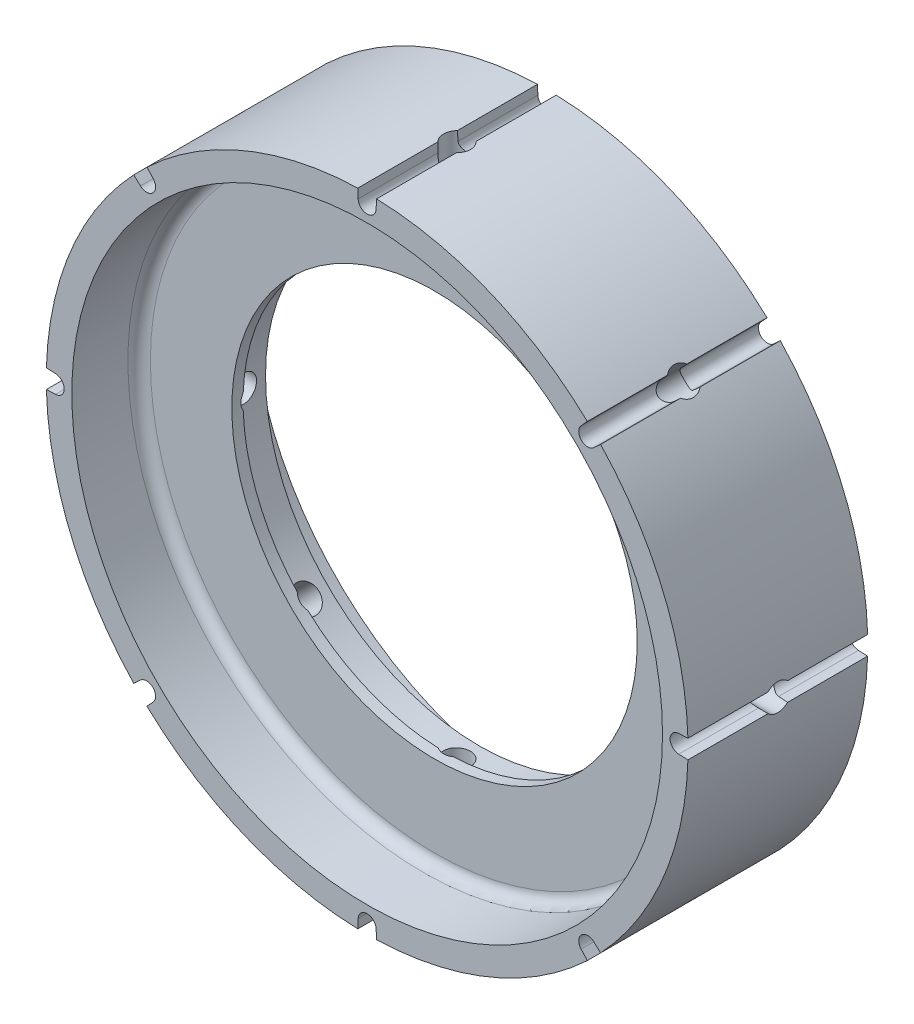
SolidWorks part; units mm, degrees
ref_plane "Front Plane" through (0, 0, 0) normal (0, 0, 1) x (1, 0, 0)
ref_plane "Top Plane" through (0, 0, 0) normal (0, 1, 0) x (1, 0, 0)
ref_plane "Right Plane" through (0, 0, 0) normal (1, 0, 0) x (0, 0, -1)
sketch "Sketch1" plane through (0, 0, 0) normal (0, 0, 1) x (1, 0, 0)
  circle A4 centre (0, 0) radius 14.2875
  circle A5 centre (0, 0) radius 13.15
  circle A6 centre (0, 0) radius 13.15
  dimension "D1" = 0.15
  dimension "D3" = 1.1375
  dimension "D2" = 28.575
extrude "Boss-Extrude1" add sketch "Sketch1" against normal blind 3
sketch "Sketch2" plane through (0, 0, 0) normal (0, 0, 1) x (1, 0, 0)
  circle A0 centre (0, 0) radius 14.2875
  circle A1 centre (0, 0) radius 9.025
  circle A2 centre (0, 0) radius 14.2875 construction
  dimension "D1" = 18.05
extrude "Boss-Extrude2" add sketch "Sketch2" along normal blind 2
sketch "Sketch3" plane through (0, 0, 2) normal (0, 0, 1) x (1, 0, 0)
  circle A0 centre (0, 0) radius 13.15 construction
  circle A1 centre (0, 0) radius 14.2875
  circle A2 centre (0, 0) radius 14.2875
  circle A3 centre (0, 0) radius 13.15
  dimension "D1" = 0
extrude "Boss-Extrude3" add sketch "Sketch3" along normal blind 3
fillet "Fillet1" radius 0.5 2 edges at (13.15, 0, 2) (13.15, 0, 0)
sketch "Sketch4" plane through (0, 0, 0) normal (0, 0, -1) x (-1, 0, 0)
  circle A1 centre (0, 0) radius 9.525
extrude "Cut-Extrude2" cut sketch "Sketch4" against normal blind 1.5
sketch "Sketch5" plane through (0, 0, -3) normal (0, 0, -1) x (-1, 0, 0)
  line L0 (-13.8709, 0.3997) -> (-14.2814, 0.4167)
  line L1 (-13.8709, -0.3997) -> (-14.2814, -0.4167)
  circle A3 centre (0, 0) radius 14.2875 construction
  circle A5 centre (0, 0) radius 14.2875
  circle A6 centre (-13.8875, 0) radius 0.4
  circle M4 centre (0, 0) radius 14.2875
extrude "Cut-Extrude4" cut sketch "Sketch5" against normal through all contours A6 | A6 L0 M4 | A6 A5 L1 region at (14.1918, 0.3195, -3) region at (13.8875, 0, -3) region at (14.1918, -0.3195, -3)
ref_plane "Plane1" through (14.2814, 0, 0) normal (1, 0, 0) x (0, 0, -1)
sketch "Sketch6" plane through (14.2814, 0, 0) normal (1, 0, 0) x (0, 0, -1)
  line L0 (-5, 0.4167) -> (3, 0.4167) construction
  line L1 (-5, 0.4167) -> (3, 0.4167)
  circle A0 centre (-1, 0) radius 0.6
  point P4 (-1, 0)
extrude "Cut-Extrude5" cut sketch "Sketch6" against normal blind 10 contours L1 A0 | L1 A0 region at (14.2814, 0.4911, 1) region at (14.2814, -0.0525, 1)
sketch "Sketch7" plane through (0, 0, 0) normal (0, 1, 0) x (1, 0, 0)
  line L0 (0, 0) -> (0, 6.608) construction
pattern_circular "CirPattern1" count 8 over 360 about axis through (0, 0, 0) along (0, 0, -1) of "Cut-Extrude5", "Cut-Extrude4"
